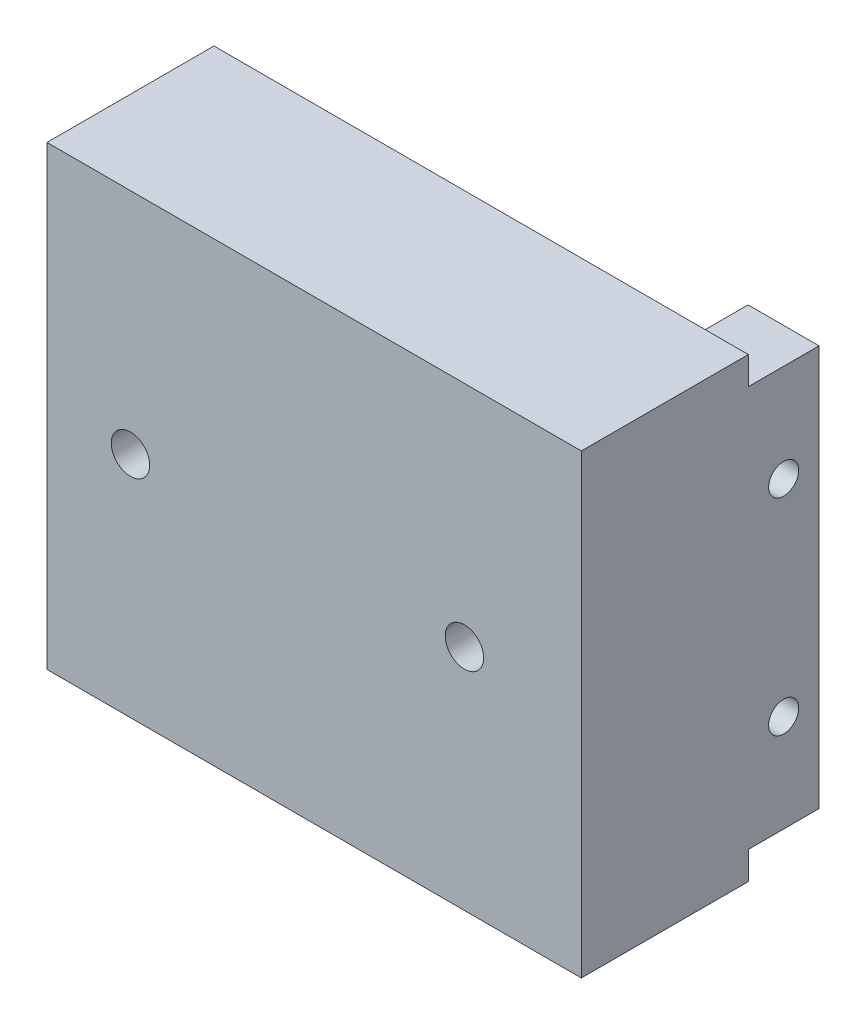
SolidWorks part; units mm, degrees
material "6061 Alloy"
ref_plane "Front Plane" through (0, 0, 0) normal (0, 0, 1) x (1, 0, 0)
ref_plane "Top Plane" through (0, 0, 0) normal (0, 1, 0) x (1, 0, 0)
ref_plane "Right Plane" through (0, 0, 0) normal (1, 0, 0) x (0, 0, -1)
sketch "Sketch1" plane through (0, 0, 0) normal (0, 0, 1) x (1, 0, 0)
  line L0 (19.125, 20.5) -> (19.125, -20.5)
  line L1 (19.125, 18) -> (25.5, 18)
  line L2 (-22.5, -20.5) -> (-22.5, 20.5)
  line L3 (19.125, -18) -> (25.5, -18)
  line L5 (-22.5, -20.5) -> (25.5, -20.5)
  line L6 (25.5, -20.5) -> (25.5, 20.5)
  line L8 (25.5, 20.5) -> (-22.5, 20.5)
  circle A4 centre (-15, 0) radius 1.5
  circle A5 centre (15, 0) radius 1.5
  point P0 (0, 0)
  dimension "D3" = 15
  dimension "D4" = 22.5
  dimension "D5" = 3
  dimension "D6" = 20.5
  dimension "D2" = 3
  dimension "D1" = 15
  dimension "D7" = 20.5
  dimension "D8" = 20.5
  dimension "D9" = 25.5
  dimension "D10" = 20.5
  dimension "D11" = 6.375
  dimension "D12" = 2.5
  dimension "D13" = 2.5
extrude "Base Extrusion" add sketch "Sketch1" along normal blind 15 contours L2 L8 L6 L5
extrude "Clearance Extension" add sketch "Sketch1<14>" against normal blind 6.35 contours L3 L6 L1 L0 region at (22.3125, 0, 0)
sketch "Sketch1<14>" plane through (0, 0, 0) normal (0, 0, 1) x (1, 0, 0) same geometry as "Sketch1"
hole_wizard "#8-32 Tapped Hole6" positions "3DSketch11" profile "Sketch14" tap size "#8-32" standard "Ansi Inch"
sketch3d "3DSketch11"
  line L1 (-22.5, -20.5, 15) -> (-22.5, 20.5, 15) construction
  line L11 (-22.5, -20.5, 15) -> (25.5, -20.5, 15) construction
  line L12 (25.5, 20.5, 15) -> (-22.5, 20.5, 15) construction
  point P0 (15, 0, 15)
  point P10 (-15, 0, 15)
  dimension "D1" = 37.5
  dimension "D2" = 20.5
  dimension "D3" = 7.5
  dimension "D4" = 20.5
cosmetic thread "Hole Thread2"
cosmetic thread "Hole Thread9"
sketch "Sketch14" plane through (15, 0, 15) normal (1, 0, 0) x (0, -1, 0)
  line L0 (0, 0) -> (0, 14.9978)
  line L1 (0, 14.9978) -> (1.7272, 13.96)
  line L2 (1.7272, 13.96) -> (1.7272, 0)
  line L5 (1.7272, 0) -> (0, 0)
  line L10 (0, 14.9978) -> (-1.7272, 13.96) construction
  line L11 (0, -6.35) -> (0, 107.95) construction
  dimension "Tap Drill Dia." = 3.4544
  dimension "Tap Drill Depth" = 13.96
  dimension "Drill Angle" = 118
hole_wizard "#6-32 Tapped Hole1" positions "Sketch25" profile "Sketch24" tap size "#6-32" standard "Ansi Inch" end condition through all
sketch "Sketch25" plane through (25.5, 0, 0) normal (1, 0, 0) x (0, 0, -1)
  line L0 (6.35, -18) -> (6.35, 18) construction
  line L1 (6.35, 18) -> (0, 18) construction
  line L2 (6.35, -18) -> (0, -18) construction
  point P0 (3.175, 9.25)
  point P1 (3.175, -9.25)
  dimension "D1" = 3.175
  dimension "D2" = 3.175
  dimension "D3" = 8.75
  dimension "D4" = 8.75
sketch "Sketch24" plane through (25.5, 9.25, -3.175) normal (0, 1, 0) x (0, 0, -1)
  line L0 (0, 0) -> (0, 48)
  line L1 (0, 48) -> (1.3525, 48)
  line L2 (1.3525, 48) -> (1.3525, 0)
  line L5 (1.3525, 0) -> (0, 0)
  line L11 (0, -6.35) -> (0, 107.95) construction
  dimension "Thru Tap Drill Dia." = 2.7051
  dimension "Thru Tap Drill Depth" = 48
cosmetic thread "Hole Thread18"
cosmetic thread "Hole Thread19"
